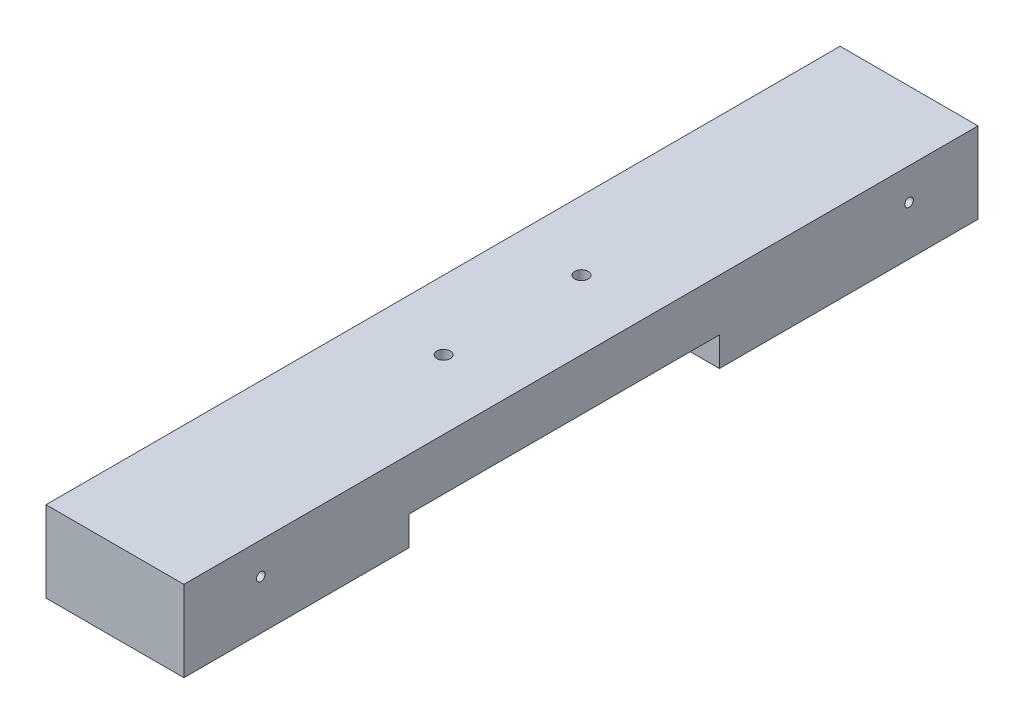
SolidWorks part; units mm, degrees
material "McMaster 6061-T6"
ref_plane "Front" through (0, 0, 0) normal (0, 0, 1) x (1, 0, 0)
ref_plane "Top" through (0, 0, 0) normal (0, 1, 0) x (1, 0, 0)
ref_plane "Right" through (0, 0, 0) normal (1, 0, 0) x (0, 0, -1)
sketch "Sketch1" plane through (0, 0, 0) normal (0, 0, 1) x (1, 0, 0)
  line L1 (0, 0) -> (101.6, 0)
  line L2 (0, 0) -> (0, 59.6)
  line L3 (0, 59.6) -> (101.6, 59.6)
  line L4 (101.6, 0) -> (101.6, 59.6)
  dimension "D1" = 59.6
  dimension "D2" = 101.6
extrude "Boss-Extrude1" add sketch "Sketch1" along normal blind 585.0001
sketch "Sketch2" plane through (0, 0, 0) normal (-1, 0, 0) x (0, 0, 1)
  line L0 (190.5, 0) -> (190.5, 21.5)
  line L1 (585.0001, 0) -> (0, 0) construction
  line L2 (190.5, 21.5) -> (419.1, 21.5)
  line L3 (419.1, 21.5) -> (419.1, 0)
  line L4 (419.1, 0) -> (190.5, 0)
  line L5 (0, 59.6) -> (0, 0) construction
  dimension "D1" = 190.5
  dimension "D2" = 21.5
  dimension "D3" = 228.6
extrude "Cut-Extrude1" cut sketch "Sketch2" against normal through all
sketch "Sketch5" plane through (0, 0, 0) normal (-1, 0, 0) x (0, 0, 1)
  arc A0 (6.7, 6.6) -> (13.3, 6.6) centre (10, 6.6) ccw construction
  arc A1 (13.3, 6.6) -> (6.7, 6.6) centre (10, 6.6) ccw construction
  arc A2 (6.7, 52.6) -> (13.3, 52.6) centre (10, 52.6) ccw construction
  arc A3 (13.3, 52.6) -> (6.7, 52.6) centre (10, 52.6) ccw construction
  arc A4 (6.7, 6.6) -> (13.3, 6.6) centre (10, 6.6) ccw
  arc A5 (13.3, 6.6) -> (6.7, 6.6) centre (10, 6.6) ccw
  arc A6 (6.7, 52.6) -> (13.3, 52.6) centre (10, 52.6) ccw
  arc A7 (13.3, 52.6) -> (6.7, 52.6) centre (10, 52.6) ccw
  arc A8 (170, 31.35) -> (170, 27.85) centre (170, 29.6) ccw construction
  arc A9 (170, 27.85) -> (170, 31.35) centre (170, 29.6) ccw construction
  arc A10 (110, 27.85) -> (110, 31.35) centre (110, 29.6) ccw construction
  arc A11 (110, 31.35) -> (110, 27.85) centre (110, 29.6) ccw construction
  arc A12 (50, 27.85) -> (50, 31.35) centre (50, 29.6) ccw construction
  arc A13 (50, 31.35) -> (50, 27.85) centre (50, 29.6) ccw construction
  arc A14 (170, 31.35) -> (170, 27.85) centre (170, 29.6) ccw
  arc A15 (170, 27.85) -> (170, 31.35) centre (170, 29.6) ccw
  arc A16 (110, 27.85) -> (110, 31.35) centre (110, 29.6) ccw
  arc A17 (110, 31.35) -> (110, 27.85) centre (110, 29.6) ccw
  arc A18 (50, 27.85) -> (50, 31.35) centre (50, 29.6) ccw
  arc A19 (50, 31.35) -> (50, 27.85) centre (50, 29.6) ccw
  arc A20 (530, 27.85) -> (530, 31.35) centre (530, 29.6) ccw construction
  arc A21 (530, 31.35) -> (530, 27.85) centre (530, 29.6) ccw construction
  arc A22 (470, 27.85) -> (470, 31.35) centre (470, 29.6) ccw construction
  arc A23 (470, 31.35) -> (470, 27.85) centre (470, 29.6) ccw construction
  arc A24 (410, 27.85) -> (410, 31.35) centre (410, 29.6) ccw construction
  arc A25 (410, 31.35) -> (410, 27.85) centre (410, 29.6) ccw construction
  arc A26 (350, 27.85) -> (350, 31.35) centre (350, 29.6) ccw construction
  arc A27 (350, 31.35) -> (350, 27.85) centre (350, 29.6) ccw construction
  arc A28 (290, 27.85) -> (290, 31.35) centre (290, 29.6) ccw construction
  arc A29 (290, 31.35) -> (290, 27.85) centre (290, 29.6) ccw construction
  arc A30 (230, 27.85) -> (230, 31.35) centre (230, 29.6) ccw construction
  arc A31 (230, 31.35) -> (230, 27.85) centre (230, 29.6) ccw construction
  arc A32 (530, 27.85) -> (530, 31.35) centre (530, 29.6) ccw
  arc A33 (530, 31.35) -> (530, 27.85) centre (530, 29.6) ccw
  arc A34 (470, 27.85) -> (470, 31.35) centre (470, 29.6) ccw
  arc A35 (470, 31.35) -> (470, 27.85) centre (470, 29.6) ccw
  arc A36 (410, 27.85) -> (410, 31.35) centre (410, 29.6) ccw
  arc A37 (410, 31.35) -> (410, 27.85) centre (410, 29.6) ccw
  arc A38 (350, 27.85) -> (350, 31.35) centre (350, 29.6) ccw
  arc A39 (350, 31.35) -> (350, 27.85) centre (350, 29.6) ccw
  arc A40 (290, 27.85) -> (290, 31.35) centre (290, 29.6) ccw
  arc A41 (290, 31.35) -> (290, 27.85) centre (290, 29.6) ccw
  arc A42 (230, 27.85) -> (230, 31.35) centre (230, 29.6) ccw
  arc A43 (230, 31.35) -> (230, 27.85) centre (230, 29.6) ccw
  arc A44 (582.3, 6.6) -> (575.7, 6.6) centre (579, 6.6) ccw construction
  arc A45 (575.7, 6.6) -> (582.3, 6.6) centre (579, 6.6) ccw construction
  arc A46 (562.7, 6.6) -> (569.3, 6.6) centre (566, 6.6) ccw construction
  arc A47 (569.3, 6.6) -> (562.7, 6.6) centre (566, 6.6) ccw construction
  arc A48 (575.7, 52.6) -> (582.3, 52.6) centre (579, 52.6) ccw construction
  arc A49 (582.3, 52.6) -> (575.7, 52.6) centre (579, 52.6) ccw construction
  arc A50 (562.7, 52.6) -> (569.3, 52.6) centre (566, 52.6) ccw construction
  arc A51 (569.3, 52.6) -> (562.7, 52.6) centre (566, 52.6) ccw construction
  arc A52 (582.3, 6.6) -> (575.7, 6.6) centre (579, 6.6) ccw
  arc A53 (575.7, 6.6) -> (582.3, 6.6) centre (579, 6.6) ccw
  arc A54 (562.7, 6.6) -> (569.3, 6.6) centre (566, 6.6) ccw
  arc A55 (569.3, 6.6) -> (562.7, 6.6) centre (566, 6.6) ccw
  arc A56 (575.7, 52.6) -> (582.3, 52.6) centre (579, 52.6) ccw
  arc A57 (582.3, 52.6) -> (575.7, 52.6) centre (579, 52.6) ccw
  arc A58 (562.7, 52.6) -> (569.3, 52.6) centre (566, 52.6) ccw
  arc A59 (569.3, 52.6) -> (562.7, 52.6) centre (566, 52.6) ccw
extrude "Cut-Extrude4" cut sketch "Sketch5" against normal blind 6.35 from surface contours A32 A33 | A34 A35 | A36 A37 | A38 A39 | A40 A41 | A42 A43 | A15 A14 | A16 A17 | A18 A19 starting at face at (0, 20.275, 298.65)
extrude "Cut-Extrude5" cut sketch "Sketch5<3>" against normal blind 25.4 from surface contours A54 A55 | A52 A53 | A56 A57 | A58 A59 | A4 A5 | A6 A7 region at (0, 6.6, 10) region at (0, 52.6, 10) region at (0, 6.6, 579) region at (0, 6.6, 566) region at (0, 52.6, 579) region at (0, 52.6, 566) starting at face at (0, 29.6, 528.25)
sketch "Sketch5<3>" plane through (0, 0, 0) normal (-1, 0, 0) x (0, 0, 1) same geometry as "Sketch5"
sketch "Sketch6" plane through (0, 21.5, 0) normal (0, -1, 0) x (1, 0, 0)
  circle A0 centre (50.8, 342.9) radius 4.9344 construction
  circle A1 centre (50.8, 241.3) radius 4.9344 construction
  circle A2 centre (50.8, 342.9) radius 4.9344
  circle A3 centre (50.8, 241.3) radius 4.9344
extrude "Cut-Extrude6" cut sketch "Sketch6" against normal through all
sketch "Sketch7" plane through (101.6, 0, 0) normal (1, 0, 0) x (0, 0, -1)
  arc A0 (-53.5485, 34.6067) -> (-48.0559, 34.6067) centre (-50.8022, 36.1999) ccw construction
  arc A1 (-53.5485, 37.7931) -> (-53.5485, 34.6067) centre (-50.8022, 36.1999) ccw construction
  arc A2 (-48.0559, 37.7931) -> (-53.5485, 37.7931) centre (-50.8022, 36.1999) ccw construction
  arc A3 (-48.0559, 34.6067) -> (-48.0559, 37.7931) centre (-50.8022, 36.1999) ccw construction
  arc A4 (-53.5485, 34.6067) -> (-48.0559, 34.6067) centre (-50.8022, 36.1999) ccw
  arc A5 (-53.5485, 37.7931) -> (-53.5485, 34.6067) centre (-50.8022, 36.1999) ccw
  arc A6 (-48.0559, 37.7931) -> (-53.5485, 37.7931) centre (-50.8022, 36.1999) ccw
  arc A7 (-48.0559, 34.6067) -> (-48.0559, 37.7931) centre (-50.8022, 36.1999) ccw
  arc A8 (-525.6376, 34.6067) -> (-525.6376, 37.7931) centre (-528.384, 36.1999) ccw construction
  arc A9 (-531.1303, 34.6067) -> (-525.6376, 34.6067) centre (-528.384, 36.1999) ccw construction
  arc A10 (-531.1303, 37.7931) -> (-531.1303, 34.6067) centre (-528.384, 36.1999) ccw construction
  arc A11 (-525.6376, 37.7931) -> (-531.1303, 37.7931) centre (-528.384, 36.1999) ccw construction
  arc A12 (-525.6376, 34.6067) -> (-525.6376, 37.7931) centre (-528.384, 36.1999) ccw
  arc A13 (-531.1303, 34.6067) -> (-525.6376, 34.6067) centre (-528.384, 36.1999) ccw
  arc A14 (-531.1303, 37.7931) -> (-531.1303, 34.6067) centre (-528.384, 36.1999) ccw
  arc A15 (-525.6376, 37.7931) -> (-531.1303, 37.7931) centre (-528.384, 36.1999) ccw
extrude "Cut-Extrude7" cut sketch "Sketch7" against normal blind 6.35
